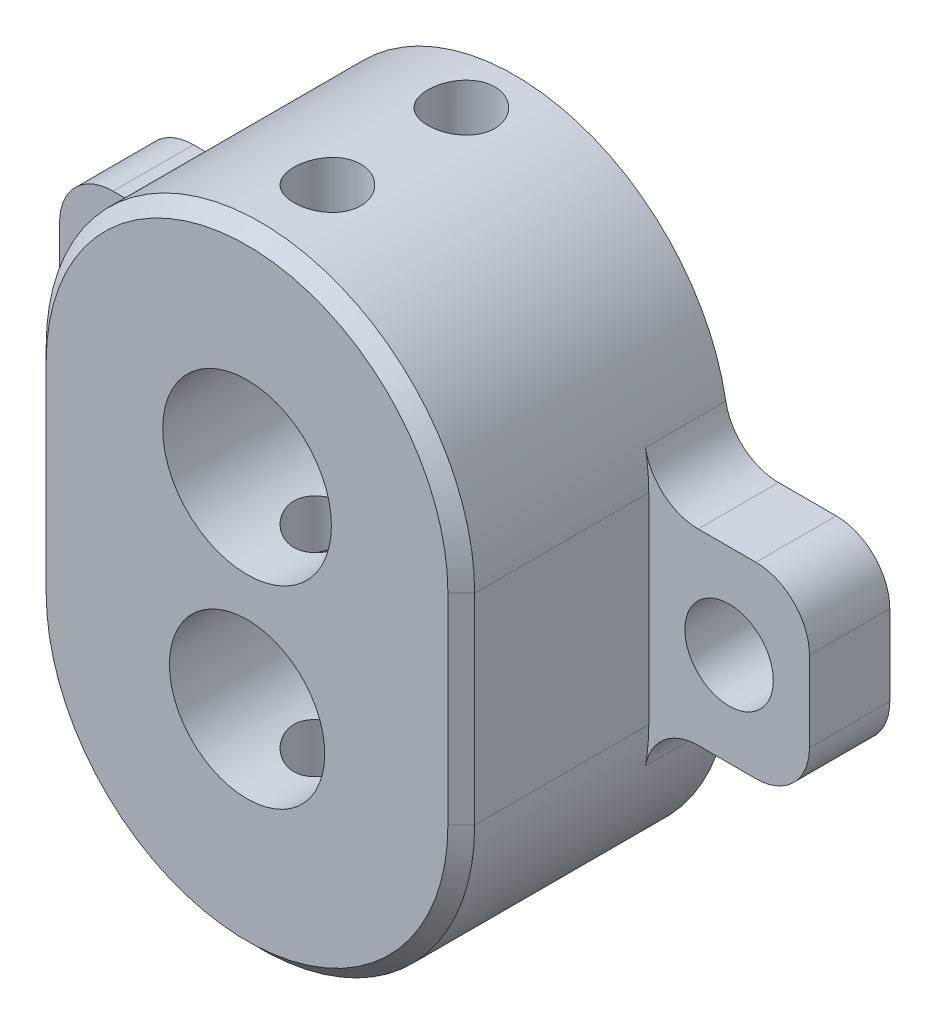
SolidWorks part; units mm, degrees
ref_plane "Front Plane" through (0, 0, 0) normal (0, 0, 1) x (1, 0, 0)
ref_plane "Top Plane" through (0, 0, 0) normal (0, 1, 0) x (1, 0, 0)
ref_plane "Right Plane" through (0, 0, 0) normal (1, 0, 0) x (0, 0, -1)
sketch "Sketch1" plane through (0, 0, 0) normal (0, 0, 1) x (1, 0, 0)
  line L0 (0, 0) -> (0, -7.5) construction
  line L1 (8, 0) -> (8, -7.5)
  line L2 (-8, 0) -> (-8, -7.5)
  arc A0 (8, 0) -> (-8, 0) centre (0, 0) ccw
  arc A1 (-8, -7.5) -> (8, -7.5) centre (0, -7.5) ccw
  circle A2 centre (0, 0) radius 3.15
  circle A3 centre (0, -7.5) radius 2.9
  point P2 (0, -3.75)
  dimension "D1" = 8
  dimension "D3" = 6.3
  dimension "D4" = 5.8
  dimension "D2" = 7.5
extrude "Boss-Extrude1" add sketch "Sketch1" along normal blind 10
sketch "Sketch2" plane through (0, 0, 0) normal (0, 1, 0) x (1, 0, 0)
  line L0 (0, 0) -> (0, -2) construction
  line L1 (8, 0) -> (-8, 0) construction
  line L2 (0, -2) -> (0, -7) construction
  circle A0 centre (0, -2) radius 1.25
  circle A1 centre (0, -7) radius 1.25
  dimension "D1" = 2.5
  dimension "D2" = 2.5
  dimension "D3" = 2
  dimension "D4" = 5
extrude "Cut-Extrude1" cut sketch "Sketch2" along normal through all
chamfer "Chamfer1" distance 0.5 angle 45 4 edges at (0, -15.5, 10) (8, -3.75, 10) (-8, -3.75, 10) (0, 8, 10)
sketch "Sketch3" plane through (0, 0, 0) normal (0, 1, 0) x (1, 0, 0)
  circle A0 centre (0, -7) radius 1.25 construction
  circle A1 centre (0, -7) radius 1.25
extrude "Cut-Extrude2" cut sketch "Sketch3" against normal through all
sketch "Sketch4" plane through (0, 0, 0) normal (0, 0, -1) x (-1, 0, 0)
  line L5 (-8, -7.5) -> (-8, 0) construction
  line L6 (-8, -0.25) -> (-14, -0.25)
  line L7 (-8, -0.25) -> (-8, -7.25)
  line L8 (-8, -7.25) -> (-14, -7.25)
  line L9 (-14, -0.25) -> (-14, -7.25)
  line L10 (-14, -3.75) -> (8, -3.75) construction
  line L11 (8, 0) -> (8, -7.5) construction
  dimension "D1" = 7
  dimension "D2" = 14
extrude "Boss-Extrude2" add sketch "Sketch4" against normal blind 3
sketch "Sketch5" plane through (0, 0, 0) normal (0, 0, -1) x (-1, 0, 0)
  line L0 (8, -3.75) -> (-11, -3.75) construction
  line L1 (8, 0) -> (8, -7.5) construction
  circle A0 centre (-11, -3.75) radius 1.65
  dimension "D2" = 3.3
  dimension "D1" = 11
extrude "Cut-Extrude3" cut sketch "Sketch5" against normal through all
fillet "Fillet1" radius 2 2 edges at (14, -7.25, 1.5) (14, -0.25, 1.5)
mirror "Mirror1" about plane through (0, 0, 0) normal (1, 0, 0) of "Cut-Extrude3", "Fillet1", "Boss-Extrude2"
fillet "Fillet2" radius 2 4 edges at (-8, -0.25, 1.5) (-8, -7.25, 1.5) (8, -7.25, 1.5) (8, -0.25, 1.5)
sketch "Sketch6" plane through (0, 0, 0) normal (0, 0, -1) x (-1, 0, 0)
  line L0 (0, 0) -> (0, -7.5) construction
  line L1 (3.5, 0) -> (3.5, -7.5)
  line L2 (-3.5, 0) -> (-3.5, -7.5)
  arc A0 (3.5, 0) -> (-3.5, 0) centre (0, 0) ccw
  arc A1 (-3.5, -7.5) -> (3.5, -7.5) centre (0, -7.5) ccw
  point P4 (0, -3.75)
  dimension "D1" = 3.5
extrude "Cut-Extrude4" cut sketch "Sketch6" against normal blind 5
